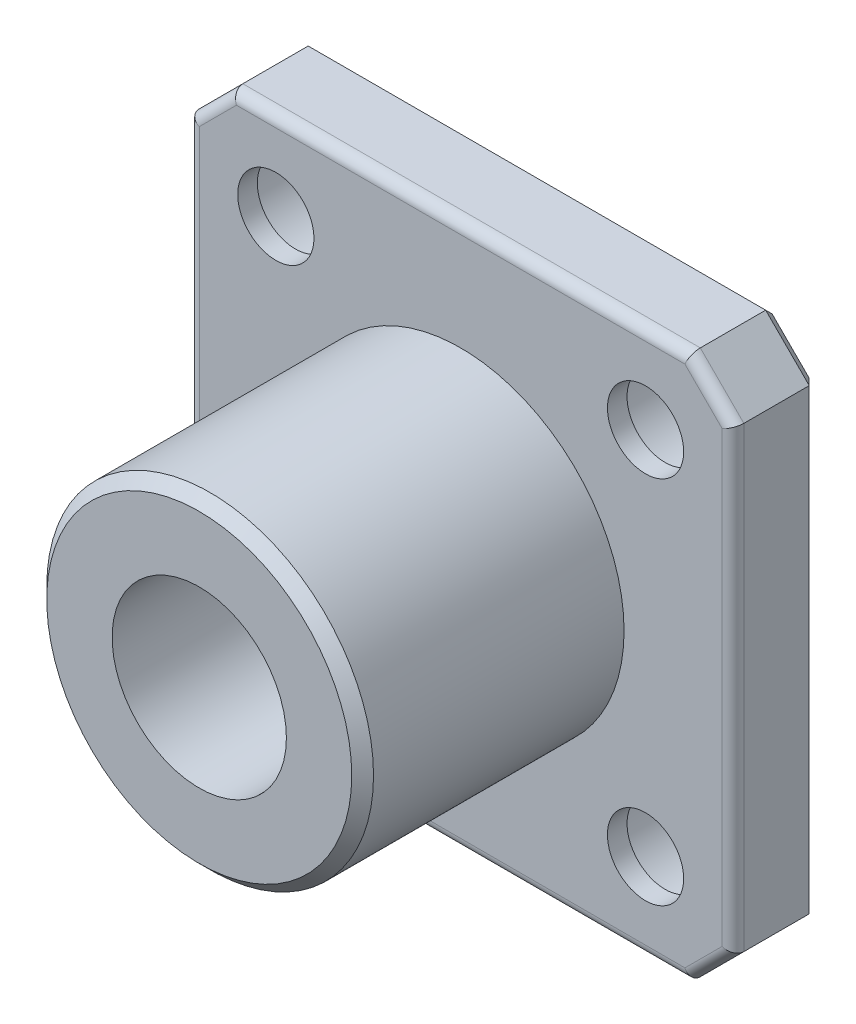
SolidWorks part; units mm, degrees
ref_plane "정면" through (0, 0, 0) normal (0, 0, 1) x (1, 0, 0)
ref_plane "윗면" through (0, 0, 0) normal (0, 1, 0) x (1, 0, 0)
ref_plane "우측면" through (0, 0, 0) normal (1, 0, 0) x (0, 0, -1)
sketch "스케치1" plane through (0, 0, 0) normal (0, 0, 1) x (1, 0, 0)
  line L0 (-12.5, 10.5) -> (-10.5, 12.5)
  line L1 (-10.5, -12.5) -> (10.5, -12.5)
  line L2 (-12.5, -10.5) -> (-12.5, 10.5)
  line L3 (-10.5, 12.5) -> (10.5, 12.5)
  line L4 (12.5, -10.5) -> (12.5, 10.5)
  line L5 (-12.5, -12.5) -> (12.5, 12.5) construction
  line L6 (-12.5, 12.5) -> (12.5, -12.5) construction
  line L7 (-12.5, -10.5) -> (-10.5, -12.5)
  line L8 (10.5, -12.5) -> (12.5, -10.5)
  line L9 (10.5, 12.5) -> (12.5, 10.5)
  line L11 (-8.4853, -8.4853) -> (8.4853, -8.4853) construction
  line L12 (-8.4853, -8.4853) -> (-8.4853, 8.4853) construction
  line L13 (-8.4853, 8.4853) -> (8.4853, 8.4853) construction
  line L14 (8.4853, -8.4853) -> (8.4853, 8.4853) construction
  line L15 (-8.4853, -8.4853) -> (8.4853, 8.4853) construction
  line L16 (-8.4853, 8.4853) -> (8.4853, -8.4853) construction
  circle A0 centre (0, 0) radius 12 construction
  circle A1 centre (-8.4853, 8.4853) radius 3
  circle A2 centre (-8.4853, -8.4853) radius 3
  circle A3 centre (8.4853, -8.4853) radius 3
  circle A4 centre (8.4853, 8.4853) radius 3
  circle A5 centre (-8.4853, 8.4853) radius 1.75
  circle A6 centre (-8.4853, -8.4853) radius 1.75
  circle A7 centre (8.4853, -8.4853) radius 1.75
  circle A8 centre (8.4853, 8.4853) radius 1.75
  circle A9 centre (0, 0) radius 4
  point P0 (0, 0)
  point P14 (0, 0)
  dimension "D2" = 24
  dimension "D3" = 6
  dimension "D4" = 3.5
  dimension "D9" = 8
  dimension "D1" = 25
extrude "보스-돌출1" add sketch "스케치1" along normal blind 4 contours L9 L3 L0 L2 L7 L1 L8 L4 A9 A4 A3 A2 A1 | A1 A5 | A4 A8 | A2 A6 | A3 A7 region at (-11.25, 11.25, 0) region at (-11.4004, 8.4853, 0) region at (-11.4004, -8.4853, 0) region at (5.5701, -8.4853, 0) region at (5.5701, 8.4853, 0)
extrude "컷-돌출1" cut sketch "스케치1<3>" along normal blind 3.1 contours A3 A7 | A2 A6 | A1 A5 | A4 A8 region at (-11.4004, 8.4853, 0) region at (-11.4004, -8.4853, 0) region at (5.5701, -8.4853, 0) region at (5.5701, 8.4853, 0)
sketch "스케치1<3>" plane through (0, 0, 0) normal (0, 0, 1) x (1, 0, 0) same geometry as "스케치1"
sketch "스케치2" plane through (0, 0, 4) normal (0, 0, 1) x (1, 0, 0)
  circle A0 centre (0, 0) radius 4 construction
  circle A1 centre (0, 0) radius 4
  circle A2 centre (0, 0) radius 7.5
  dimension "D1" = 15
extrude "보스-돌출2" add sketch "스케치2" along normal blind 12
chamfer "모따기1" distance 0.5 angle 45 1 edges at (7.5, 0, 16)
chamfer "모따기2" distance 0.5 angle 45 8 edges at (-11.5, 11.5, 0) (-12.5, 0, 0) (-11.5, -11.5, 0) (0, -12.5, 0) (11.5, -11.5, 0) (12.5, 0, 0) (11.5, 11.5, 0) (0, 12.5, 0)
fillet "필렛1" radius 0.5 8 edges at (-11.5, -11.5, 4) (0, -12.5, 4) (11.5, -11.5, 4) (11.5, 11.5, 4) (12.5, 0, 4) (-12.5, 0, 4) (-11.5, 11.5, 4) (0, 12.5, 4)
